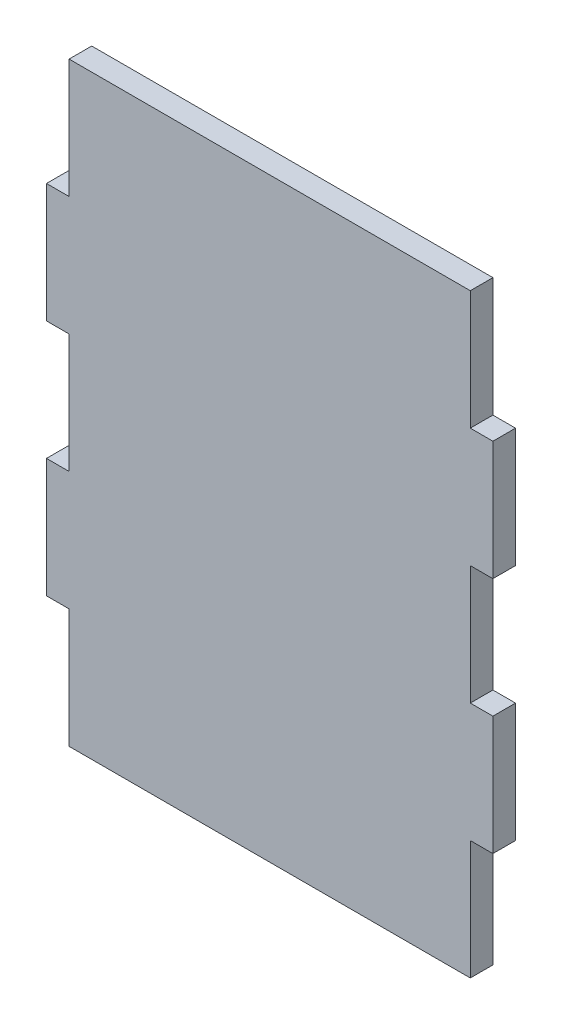
SolidWorks part; units mm, degrees
material "1060 Alloy"
ref_plane "Front Plane" through (0, 0, 0) normal (0, 0, 1) x (1, 0, 0)
ref_plane "Top Plane" through (0, 0, 0) normal (0, 1, 0) x (1, 0, 0)
ref_plane "Right Plane" through (0, 0, 0) normal (1, 0, 0) x (0, 0, -1)
sketch "Sketch1" plane through (0, 0, 0) normal (0, 0, 1) x (1, 0, 0)
  line L0 (0, 76.2) -> (0, 101.6)
  line L1 (4.826, 0) -> (90.424, 0)
  line L2 (0, 25.4) -> (0, 50.8)
  line L3 (4.826, 127) -> (90.424, 127)
  line L4 (95.25, 25.4) -> (95.25, 50.8)
  line L6 (0, 0) -> (95.25, 0) construction
  line L7 (0, 101.6) -> (4.826, 101.6)
  line L8 (4.826, 127) -> (4.826, 101.6)
  line L9 (0, 25.4) -> (4.826, 25.4)
  line L10 (0, 0) -> (0, 127) construction
  line L12 (4.826, 25.4) -> (4.826, 0)
  line L13 (0, 76.2) -> (4.826, 76.2)
  line L15 (0, 50.8) -> (4.826, 50.8)
  line L16 (4.826, 76.2) -> (4.826, 50.8)
  line L18 (90.424, 127) -> (90.424, 101.6)
  line L19 (90.424, 101.6) -> (95.25, 101.6)
  line L21 (95.25, 76.2) -> (90.424, 76.2)
  line L23 (95.25, 50.8) -> (90.424, 50.8)
  line L24 (90.424, 76.2) -> (90.424, 50.8)
  line L25 (95.25, 25.4) -> (90.424, 25.4)
  line L28 (90.424, 25.4) -> (90.424, 0)
  line L29 (95.25, 76.2) -> (95.25, 101.6)
  line L30 (0, 127) -> (95.25, 127) construction
  line L31 (95.25, 0) -> (95.25, 127) construction
  dimension "D1" = 95.25
  dimension "D2" = 127
  dimension "D3" = 4.826
extrude "Boss-Extrude1" add sketch "Sketch1" along normal blind 4.826
equation "\"sheet width\"= .19"
equation "\"width\"= 24.5"
equation "\"length\"= 34.5"
equation "\"standoff hole size\"= .5"
equation "\"ground clearence\"= 3"
equation "\"small drive pulley\"= 74.55mm"
equation "\"large drive pulley\"= 150.95mm"
equation "\"drive axle hole size\"= .5"
equation "\"front pulley clearence\"= 1"
equation "\"center support location\"= 19"
equation "\"inner to outer wall size\"= 3.75"
equation "\"D1@Sketch1\"=\"inner to outer wall size\""
equation "\"D3@Sketch1\"=\"sheet width\""
equation "\"D1@Boss-Extrude1\"=\"sheet width\""
